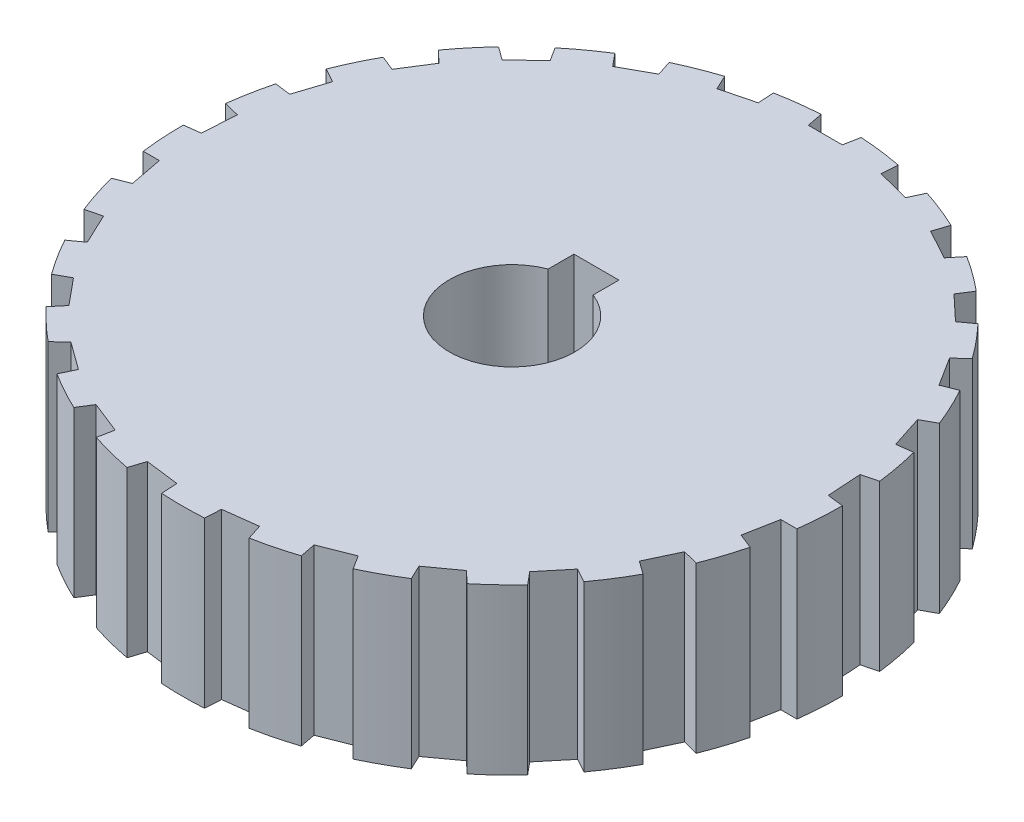
SolidWorks part; units mm, degrees
ref_plane "Front Plane" through (0, 0, 0) normal (0, 0, 1) x (1, 0, 0)
ref_plane "Top Plane" through (0, 0, 0) normal (0, 1, 0) x (1, 0, 0)
ref_plane "Right Plane" through (0, 0, 0) normal (1, 0, 0) x (0, 0, -1)
sketch "Sketch5" plane through (0, 0, 0) normal (0, 1, 0) x (1, 0, 0)
  circle A0 centre (0, 0) radius 38.1
  point P2 (0, 0)
extrude "Boss-Extrude2" add sketch "Sketch5" along normal blind 19.05
sketch "Sketch8" plane through (0, 19.05, 0) normal (0, 1, 0) x (1, 0, 0)
  line L0 (0.0089, 38.105) -> (2.333, 38.105)
  line L1 (0.0089, 38.105) -> (-2.3152, 38.105)
  line L2 (-1.9568, 36.2) -> (1.9746, 36.2)
  line L3 (2.333, 38.105) -> (1.9746, 36.2)
  line L4 (-2.3152, 38.105) -> (-1.9568, 36.2)
  circle A0 centre (0, 0) radius 38.1 construction
  point P0 (0, 38.1)
  point P1 (0, 0)
  point P4 (0, 0)
  dimension "D1" = 36.2
  dimension "D2" = 1.905
extrude "Cut-Extrude1" cut sketch "Sketch8" against normal blind 22.05
pattern_circular "CirPattern1" count 25 over 360 about axis through (0, 19.05, 0) along (0, 1, 0) of "Cut-Extrude1"
sketch "Sketch9" plane through (0, 19.05, 0) normal (0, 1, 0) x (1, 0, 0)
  line L0 (0, 7.25) -> (2.6, 7.25)
  line L1 (0, 7.25) -> (-2.6, 7.25)
  line L2 (-2.6, 7.25) -> (-2.6, 6.7678)
  line L3 (2.6, 7.25) -> (2.6, 6.7678)
  line L4 (-2.6, 7.25) -> (-2.6, 9.75)
  line L5 (-2.6, 9.75) -> (2.6, 9.75)
  line L6 (2.6, 9.75) -> (2.6, 7.25)
  circle A0 centre (0, 0) radius 7.25
extrude "Cut-Extrude2" cut sketch "Sketch9" against normal blind 25.4 contours A0 | L6 L5 L4 L1 L0 | A0 L1 L2 | A0 L3 L0 region at (0, 19.05, -8.5) region at (-1.9544, 19.05, -7.1062) region at (1.9544, 19.05, -7.1062) region at (0, 19.05, 0)
